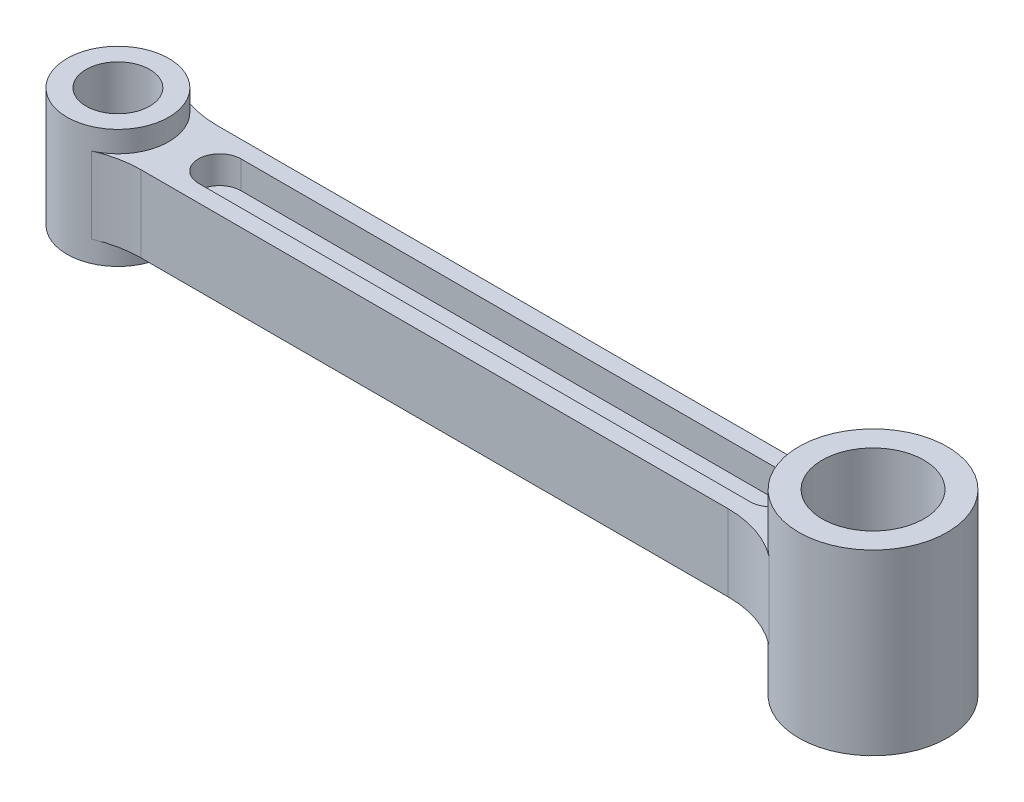
SolidWorks part; units mm, degrees
ref_plane "Front Plane" through (0, 0, 0) normal (0, 0, 1) x (1, 0, 0)
ref_plane "Top Plane" through (0, 0, 0) normal (0, 1, 0) x (1, 0, 0)
ref_plane "Right Plane" through (0, 0, 0) normal (1, 0, 0) x (0, 0, -1)
sketch "Sketch1" plane through (0, 0, 0) normal (0, 1, 0) x (1, 0, 0)
  line L0 (0, 0) -> (178, 0) construction
  line L1 (14.3875, 9) -> (152.8355, 9)
  line L2 (14.3875, -9) -> (152.8355, -9)
  line L3 (24, 0) -> (154, 0) construction
  line L4 (24, 5) -> (154, 5)
  line L5 (24, -5) -> (154, -5)
  arc A0 (4.7958, 11) -> (4.7958, -11) centre (0, 0) ccw
  circle A1 centre (0, 0) radius 7.5
  arc A2 (167.3885, -13.9157) -> (167.3885, 13.9157) centre (178, 0) ccw
  circle A3 centre (178, 0) radius 12
  arc A4 (4.7958, 11) -> (14.3875, 9) centre (14.3875, 33) ccw
  arc A5 (152.8355, 9) -> (167.3885, 13.9157) centre (152.8355, 33) ccw
  arc A6 (152.8355, -9) -> (167.3885, -13.9157) centre (152.8355, -33) cw
  arc A7 (4.7958, -11) -> (14.3875, -9) centre (14.3875, -33) cw
  arc A8 (24, 5) -> (24, -5) centre (24, 0) ccw
  arc A9 (154, -5) -> (154, 5) centre (154, 0) ccw
  arc A10 (4.7958, 11) -> (4.7958, -11) centre (0, 0) cw
  arc A11 (167.3885, 13.9157) -> (167.3885, -13.9157) centre (178, 0) ccw
  point P19 (89, 0)
  dimension "D1" = 24
  dimension "D2" = 15
  dimension "D3" = 35
  dimension "D4" = 24
  dimension "D6" = 9
  dimension "D9" = 24
  dimension "D10" = 24
  dimension "D5" = 178
  dimension "D7" = 10
  dimension "D8" = 130
extrude "Boss-Extrude4" add sketch "Sketch1" along normal mid plane 42 contours A2 A11 A3 region at (195.005, 0, 0)
extrude "Boss-Extrude5" add sketch "Sketch1<6>" along normal mid plane 28 separate body contours A10 A0 A1 region at (11.6606, 0, 0)
sketch "Sketch1<6>" plane through (0, 0, 0) normal (0, 1, 0) x (1, 0, 0) same geometry as "Sketch1"
extrude "Boss-Extrude6" add sketch "Sketch1<7>" along normal mid plane 18 contours A11 A5 L1 A4 A10 A7 L2 A6 A9 L5 A8 L4 region at (83.6115, 0, -7.3504)
sketch "Sketch1<7>" plane through (0, 0, 0) normal (0, 1, 0) x (1, 0, 0) same geometry as "Sketch1"
extrude "Boss-Extrude7" add sketch "Sketch1<8>" along normal mid plane 5 contours L5 A9 L4 A8 region at (89, 0, 0)
sketch "Sketch1<8>" plane through (0, 0, 0) normal (0, 1, 0) x (1, 0, 0) same geometry as "Sketch1"
sketch "Sketch2" plane through (0, 0, 0) normal (0, 1, 0) x (1, 0, 0)
  line L0 (0, 0) -> (178, 0) construction
